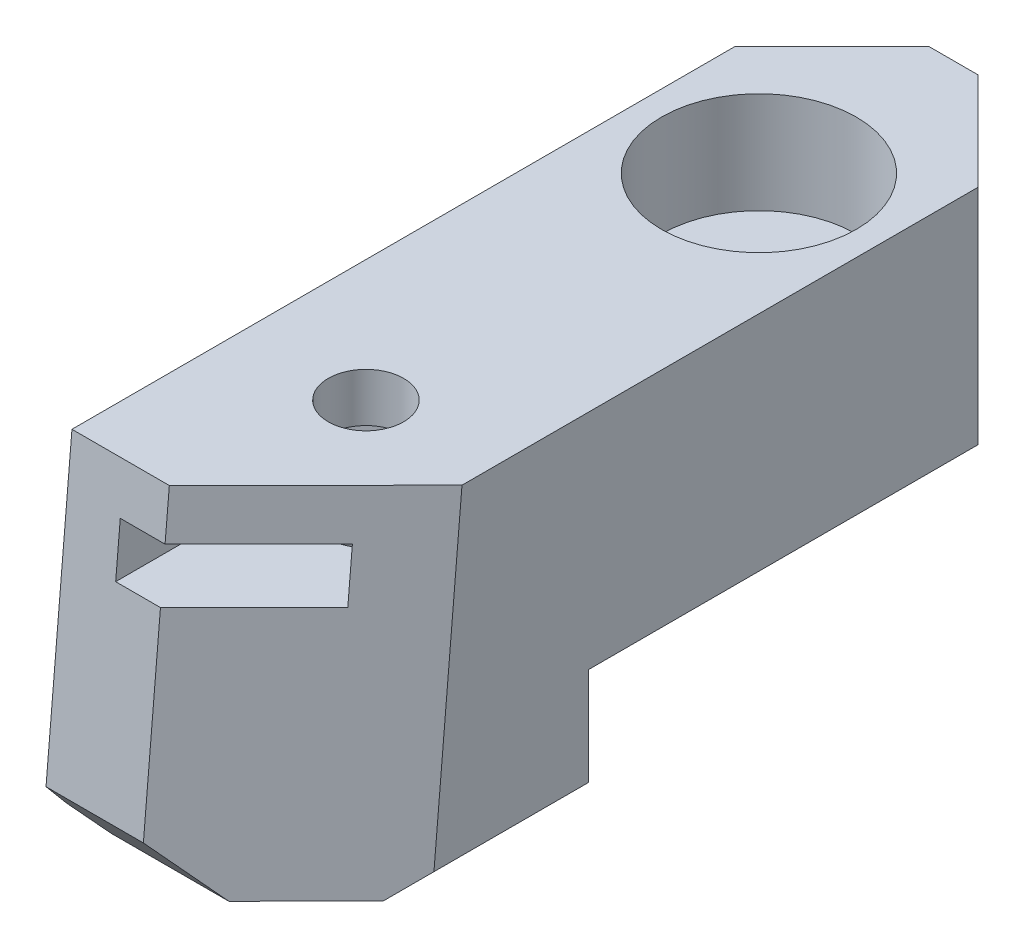
SolidWorks part; units mm, degrees
material "PET"
ref_plane "Front Plane" through (0, 0, 0) normal (0, 0, 1) x (1, 0, 0)
ref_plane "Top Plane" through (0, 0, 0) normal (0, 1, 0) x (1, 0, 0)
ref_plane "Right Plane" through (0, 0, 0) normal (1, 0, 0) x (0, 0, -1)
sketch "Sketch1" plane through (0, 0, 0) normal (1, 0, 0) x (0, 0, -1)
  line L1 (12.7, -4.7625) -> (-12.7, -4.7625)
  line L2 (12.7, -4.7625) -> (12.7, 4.7625)
  line L3 (12.7, 4.7625) -> (-12.7, 4.7625)
  line L4 (-12.7, -4.7625) -> (-12.7, 4.7625)
  line L5 (12.7, -4.7625) -> (-12.7, 4.7625) construction
  line L6 (12.7, 4.7625) -> (-12.7, -4.7625) construction
  point P0 (0, 0)
  dimension "D1" = 9.525
  dimension "D2" = 25.4
extrude "Boss-Extrude1" add sketch "Sketch1" along normal mid plane 15.875
sketch "Sketch2" plane through (-7.9375, 0, 0) normal (-1, 0, 0) x (0, 0, 1)
  line L0 (12.7, 4.7625) -> (37.438, 4.7625)
  line L1 (12.7, 4.7625) -> (12.7, -4.7625) construction
  line L2 (37.438, 4.7625) -> (38.829, -11.1363)
  line L4 (38.829, -11.1363) -> (12.7, -11.1363)
  line L9 (12.7, -11.1363) -> (12.7, 4.7625)
  line L10 (-12.7, 4.7625) -> (12.7, 4.7625) construction
  line L11 (25.5674, 149.1875) -> (39.494, -9.9944) construction
  line L12 (19.05, -11.1363) -> (38.1, -11.1363) construction
  dimension "D1" = 0.762
extrude "Boss-Extrude2" add sketch "Sketch2" against normal through all
chamfer "Chamfer1" distance 6.35 angle 45 4 edges at (7.9375, -7.9494, 12.7) (7.9375, 0, -12.7) (-7.9375, 0, -12.7) (-7.9375, -7.9494, 12.7)
chamfer "Chamfer2" distance 3.175 angle 45 1 edges at (0, -11.1363, 38.829) first distance on face at (0, -3.1869, 38.1335)
hole_wizard "#8 Clearance Hole1" positions "Sketch3" profile "Sketch4" hole size "#8" standard "ANSI Inch" end condition up to next
sketch "Sketch3" plane through (0, -11.1363, 0) normal (0, -1, 0) x (-1, 0, 0)
  line L0 (0, -38.5523) -> (0, -12.7) construction
  line L1 (7.9375, -38.5523) -> (-7.9375, -38.5523) construction
  line L2 (-1.5875, -12.7) -> (1.5875, -12.7) construction
  line L3 (0, -12.7) -> (0, 12.7) construction
  line L4 (-1.5875, 12.7) -> (1.5875, 12.7) construction
  line L6 (0, 0) -> (7.9375, 0) construction
  line L7 (7.9375, -19.05) -> (7.9375, 6.35) construction
  line L9 (0, -25.6261) -> (7.9375, -25.6261) construction
  line L10 (7.9375, -19.05) -> (7.9375, -35.8983) construction
  point P35 (0, 0)
  point P36 (0, -25.6261)
  point P41 (0, 0)
  point P42 (0, 0)
  point P43 (0, -25.6261)
  point P44 (0, 0)
sketch "Sketch4" plane through (0, -11.1363, 25.6261) normal (1, 0, 0) x (0, 0, -1)
  line L0 (0, 0) -> (0, 15.8988)
  line L1 (0, 15.8988) -> (2.4574, 15.8988)
  line L2 (2.4574, 15.8988) -> (2.4574, 0)
  line L5 (2.4574, 0) -> (0, 0)
  line L11 (0, -6.35) -> (0, 107.95) construction
  dimension "Thru Hole Dia." = 4.9149
  dimension "Thru Hole Depth" = 15.8988
chamfer "Chamfer3" distance 1.5875 angle 45 10 edges at (-7.9375, -4.7625, 6.35) (-4.7625, -4.7625, -9.525) (0, -4.7625, -12.7) (4.7625, -4.7625, -9.525) (7.9375, -4.7625, 6.35) (7.9375, -11.1363, 27.4741) (4.7625, -11.1363, 15.875) (0, -11.1363, 12.7) (-4.7625, -11.1363, 15.875) (-7.9375, -11.1363, 27.4741)
sketch "Sketch5" plane through (0, 4.7625, 0) normal (0, 1, 0) x (1, 0, 0)
  line L0 (7.9375, 6.35) -> (7.9375, -37.438) construction
  line L1 (4.5085, -37.438) -> (4.5085, -23.0232)
  line L2 (4.5085, -23.0232) -> (0, -20.4202)
  line L3 (0, -20.4202) -> (-4.5085, -23.0232)
  line L4 (-4.5085, -23.0232) -> (-4.5085, -37.438)
  line L19 (7.9375, -37.438) -> (-7.9375, -37.438) construction
  line L20 (-7.9375, -37.438) -> (-4.5085, -37.438)
  line L21 (-7.9375, -37.438) -> (-7.9375, -16.9912)
  line L22 (-7.9375, -16.9912) -> (7.9375, -16.9912)
  line L23 (7.9375, -37.438) -> (7.9375, -16.9912)
  line L24 (44.3937, -56.4628) -> (48.9022, -59.0658) [skipped]
  line L25 (48.9022, -2.5984) -> (53.4107, 0.0046) [skipped]
  line L26 (4.5085, -37.438) -> (7.9375, -37.438)
  line L27 (0, -20.4202) -> (0, -16.9912) construction
  line L37 (-7.9375, 6.35) -> (-7.9375, -37.438) construction
  circle A0 centre (0, -25.6261) radius 4.5085 construction
  circle A4 centre (0, -25.6261) radius 2.4574 construction
  point P1 (0, 0)
  point P7 (0, 0)
  point P48 (0, 0)
  point P49 (-74.4739, -17.2452)
  point P51 (0, 0)
  dimension "D1" = 9.017
extrude "Boss-Extrude3" add sketch "Sketch5" along normal blind 3.429
sketch "Sketch6" plane through (0, 8.1915, 0) normal (0, 1, 0) x (1, 0, 0)
  line L9 (-7.9375, -16.9912) -> (7.9375, -16.9912)
  line L10 (-7.9375, -16.9912) -> (-7.9375, -37.438)
  line L11 (-7.9375, -37.438) -> (7.9375, -37.438)
  line L12 (7.9375, -16.9912) -> (7.9375, -37.438)
  line L13 (7.9375, -25.6261) -> (-7.9375, -25.6261) construction
  circle A0 centre (0, -25.6261) radius 2.4574 construction
  circle A3 centre (0, -25.6261) radius 2.4574
  circle A4 centre (0, -25.6261) radius 2.4574 construction
  point P4 (0, 0)
  point P32 (0, -25.6261)
extrude "Boss-Extrude4" add sketch "Sketch6" along normal blind 3.175
chamfer "Chamfer4" [suppressed] distance 6.604 angle 45
sketch "Sketch7" plane through (0, 4.7625, 0) normal (0, 1, 0) x (1, 0, 0)
  line L32 (-7.9375, 6.35) -> (-7.9375, -16.9912)
  line L33 (-7.9375, 6.35) -> (-7.9375, -16.9912)
  line L34 (-7.9375, -16.9912) -> (7.9375, -16.9912)
  line L35 (-7.9375, -16.9912) -> (7.9375, -16.9912)
  line L40 (7.9375, -16.9912) -> (7.9375, 6.35)
  line L41 (7.9375, -16.9912) -> (7.9375, 6.35)
  line L57 (7.9375, 6.35) -> (1.5875, 12.7)
  line L58 (1.5875, 12.7) -> (-1.5875, 12.7)
  line L59 (-1.5875, 12.7) -> (-7.9375, 6.35)
  line L75 (7.9375, 6.35) -> (1.5875, 12.7)
  line L76 (1.5875, 12.7) -> (-1.5875, 12.7)
  line L77 (-1.5875, 12.7) -> (-7.9375, 6.35)
  circle A0 centre (0, 0) radius 6.35
  circle A1 centre (0, 0) radius 6.35 construction
  dimension "D5" = 12.7
  dimension "D1" = 0
extrude "Boss-Extrude5" add sketch "Sketch7" along normal up to surface (6.604 mm away) up to face at (0, 11.3665, 27.2146)
sketch "Sketch8" plane through (-7.9375, 0, 0) normal (-1, 0, 0) x (0, 0, 1)
  line L0 (37.438, 4.7625) -> (36.8603, 11.3665)
  line L1 (37.438, 11.3665) -> (37.438, 4.7625) construction
  line L2 (36.8603, 11.3665) -> (37.438, 11.3665)
  line L3 (37.438, 11.3665) -> (37.438, 4.7625)
  line L4 (38.5523, -7.9734) -> (37.438, 4.7625) construction
  line L6 (-6.35, 11.3665) -> (37.438, 11.3665) construction
  point P2 (38.7359, 12.3009)
extrude "Cut-Extrude1" cut sketch "Sketch8" against normal through all
chamfer "Chamfer5" distance 9.525 angle 45 1 edges at (7.9375, 1.6966, 37.7063)
